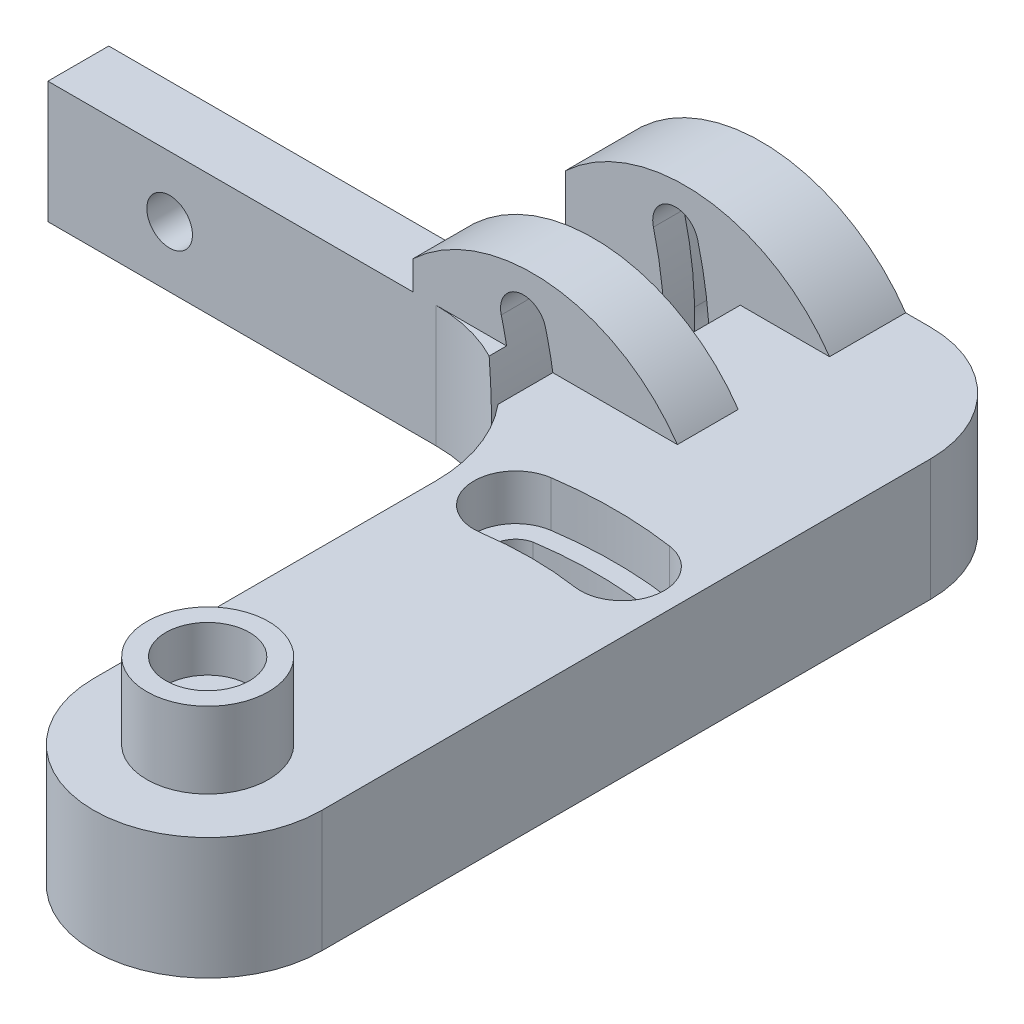
SolidWorks part; units mm, degrees
ref_plane "Front Plane" through (0, 0, 0) normal (0, 0, 1) x (1, 0, 0)
ref_plane "Top Plane" through (0, 0, 0) normal (0, 1, 0) x (1, 0, 0)
ref_plane "Right Plane" through (0, 0, 0) normal (1, 0, 0) x (0, 0, -1)
sketch "Sketch1" plane through (0, 0, 0) normal (0, 1, 0) x (1, 0, 0)
  line L0 (0, 0) -> (0, 24) construction
  line L1 (0, -7.5) -> (0, 49000) construction
  line L2 (-7.5, 36.5) -> (-43, 36.5)
  line L3 (-43, 36.5) -> (-43, 32.5)
  line L5 (7.5, 0) -> (7.5, 40)
  line L6 (0, 47.5) -> (-19, 47.5)
  line L7 (-19, 47.5) -> (-19, 42.5)
  line L8 (-19, 42.5) -> (-7.5, 42.5)
  line L9 (-43, 32.5) -> (-17.5, 32.5)
  line L11 (-7.5, 36.5) -> (-7.5, 42.5)
  line L12 (-7.5, 0) -> (-7.5, 22.5)
  circle A1 centre (0, 0) radius 1.45
  arc A3 (3.5, 23.7434) -> (-3.5, 23.7434) centre (0, 0) ccw construction
  arc A4 (-3.8223, 25.2084) -> (-3.2806, 22.2596) centre (-3.5, 23.7434) ccw
  arc A5 (3.1485, 22.2786) -> (3.8936, 25.1975) centre (3.5, 23.7434) ccw
  arc A7 (3.8936, 25.1975) -> (-3.8223, 25.2084) centre (0, 0) ccw
  arc A8 (3.1485, 22.2786) -> (-3.2806, 22.2596) centre (0, 0) ccw
  arc A9 (7.5, 40) -> (0, 47.5) centre (0, 40) ccw
  arc A16 (-7.5, 0) -> (7.5, 0) centre (0, 0) ccw
  arc A17 (-7.5, 22.5) -> (-17.5, 32.5) centre (-17.5, 22.5) ccw
  dimension "D3" = 2.9
  dimension "D6" = 3
  dimension "D7" = 40
  dimension "D8" = 15
  dimension "D10" = 6
  dimension "D11" = 10
  dimension "D2" = 24
  dimension "D4" = 3.5
  dimension "D5" = 3.5
  dimension "D9" = 5
  dimension "D13" = 26.5
  dimension "D14" = 50.5
  dimension "D15" = 4
  dimension "D17" = 7.5
extrude "Boss-Extrude1" add sketch "Sketch1" along normal blind 8
sketch "Sketch2" plane through (0, 8, 0) normal (0, 1, 0) x (1, 0, 0)
  circle A0 centre (0, 0) radius 4
  circle A2 centre (0, 0) radius 1.45
  dimension "D1" = 8
extrude "Boss-Extrude2" add sketch "Sketch2" along normal blind 2
sketch "Sketch4" plane through (0, 10, 0) normal (0, 1, 0) x (1, 0, 0)
  circle A0 centre (0, 0) radius 4
  circle A1 centre (0, 0) radius 2.75
  dimension "D1" = 5.5
  dimension "D2" = 8
extrude "Boss-Extrude3" add sketch "Sketch4" along normal blind 3
sketch "Sketch5" plane through (0, 8, 0) normal (0, 1, 0) x (1, 0, 0)
  arc A0 (-3.901, 26.464) -> (-3.099, 21.0228) centre (-3.5, 23.7434) ccw
  arc A1 (3.099, 21.0228) -> (3.901, 26.464) centre (3.5, 23.7434) ccw
  arc A2 (3.901, 26.464) -> (-3.901, 26.464) centre (0, 0) ccw
  arc A3 (3.099, 21.0228) -> (-3.099, 21.0228) centre (0, 0) ccw
  dimension "D1" = 5.5
  dimension "D2" = 5.5
extrude "Cut-Extrude1" cut sketch "Sketch5" against normal blind 3
sketch "Sketch8" plane through (0, 0, -47.5) normal (0, 0, -1) x (-1, 0, 0)
  line L2 (4, 13) -> (-4, 13) construction
  line L3 (19, 8) -> (19, 9.8957)
  line L4 (19, 8) -> (1.6312, 8)
  arc A3 (19, 9.8957) -> (1.6312, 8) centre (11.1312, 1.475) ccw
  dimension "D1" = 0
sketch "Sketch6" plane through (0, 0, -47.5) normal (0, 0, -1) x (-1, 0, 0)
  line L0 (7.5, 0) -> (43, 0) construction
  line L1 (43, 8) -> (43, 0) construction
  line L2 (35, 4) -> (-18.5053, 9.6236) construction
  line L3 (35, -996) -> (35, 49004) construction
  circle A0 centre (35, 4) radius 1.5
  circle A1 centre (11.1315, 6.5087) radius 1.5 construction
  arc A3 (13.2055, 9.59) -> (10.2995, 10.3354) centre (11.7525, 9.9627) ccw
  arc A4 (9.5221, 2.9386) -> (12.5195, 3.0635) centre (11.0208, 3.001) ccw
  arc A8 (13.2055, 9.59) -> (12.5195, 3.0635) centre (35, 4) ccw
  arc A9 (10.2995, 10.3354) -> (9.5221, 2.9386) centre (35, 4) ccw
  arc A10 (14.4163, 9.2795) -> (13.7684, 3.1155) centre (35, 4) ccw
  arc A11 (9.0887, 10.6459) -> (8.2732, 2.8866) centre (35, 4) ccw
  arc A12 (14.4163, 9.2795) -> (9.0887, 10.6459) centre (11.7525, 9.9627) ccw
  arc A13 (8.2732, 2.8866) -> (13.7684, 3.1155) centre (11.0208, 3.001) ccw
  line M6 (19, 8) -> (0, 8)
  dimension "D1" = 3
  dimension "D4" = 3
  dimension "D8" = 3
  dimension "D9" = 3
  dimension "D2" = 4
  dimension "D3" = 24
  dimension "D5" = 8
  dimension "D6" = 3.5
  dimension "D7" = 3.5
  dimension "D12" = 84
extrude "Cut-Extrude2" cut sketch "Sketch6" against normal up to next contours A3 A9 A4 A8 | A0
extrude "Cut-Extrude3" cut sketch "Sketch6<3>" against normal blind 3 contours A11 A13 A10 A12 A9 A3 A8 A4 region at (-13.7278, 6.2358, -47.5)
sketch "Sketch6<3>" plane through (0, 0, -47.5) normal (0, 0, -1) x (-1, 0, 0) same geometry as "Sketch6"
extrude "Boss-Extrude8" add sketch "Sketch8" against normal up to surface (5 mm away) up to face at (-12.1895, 4.565, -42.5)
extrude "Boss-Extrude9" add sketch "Sketch8<3>" against normal up to surface (15 mm away) from offset 11 up to face at (-36.5, 4, -32.5) offset against normal yes
sketch "Sketch8<3>" plane through (0, 0, -47.5) normal (0, 0, -1) x (-1, 0, 0) same geometry as "Sketch8"
extrude "Cut-Extrude6" cut sketch "Sketch6<6>" against normal through all contours A9 A4 A8 M6 | A3 A9 A8 M6 region at (-11.612, 9.5817, -47.5) region at (-11.078, 4.9087, -47.5)
sketch "Sketch6<6>" plane through (0, 0, -47.5) normal (0, 0, -1) x (-1, 0, 0) same geometry as "Sketch6"
extrude "Cut-Extrude7" cut sketch "Sketch6<7>" against normal blind 3
sketch "Sketch6<7>" plane through (0, 0, -47.5) normal (0, 0, -1) x (-1, 0, 0) same geometry as "Sketch6"
